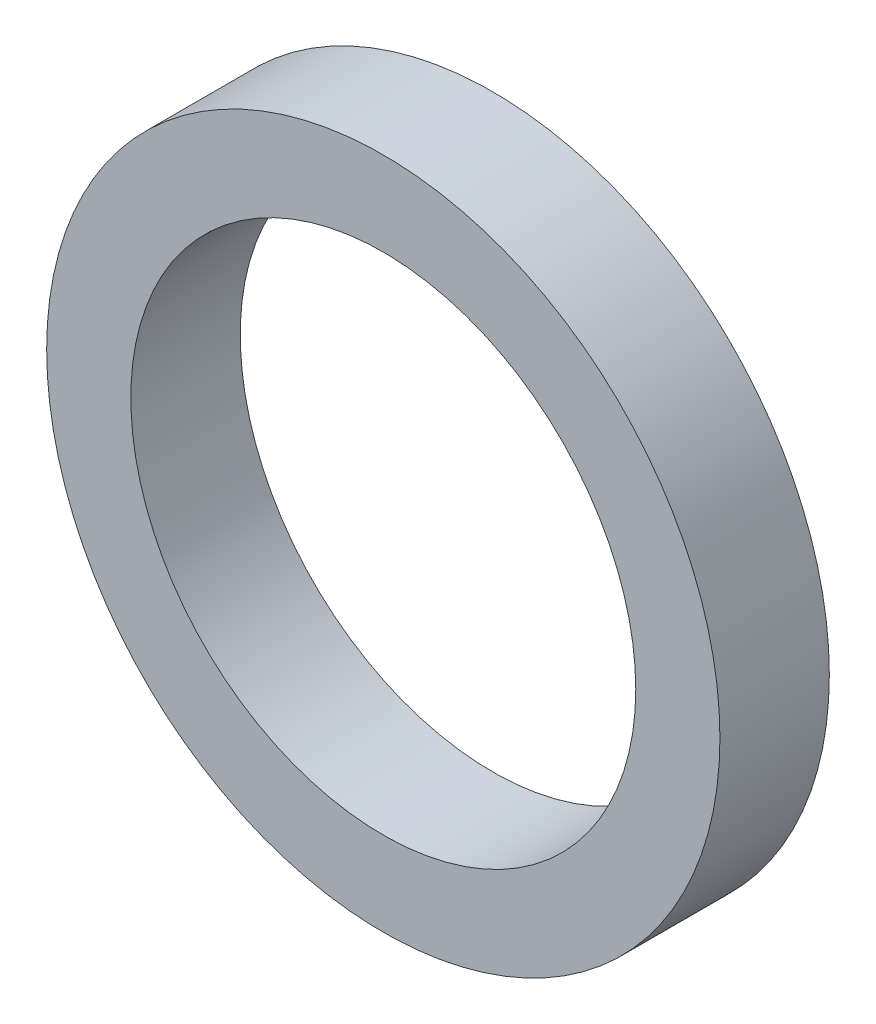
SolidWorks part; units mm, degrees
ref_plane "Płaszczyzna przednia" through (0, 0, 0) normal (0, 0, 1) x (1, 0, 0)
ref_plane "Płaszczyzna górna" through (0, 0, 0) normal (0, 1, 0) x (1, 0, 0)
ref_plane "Płaszczyzna prawa" through (0, 0, 0) normal (1, 0, 0) x (0, 0, -1)
sketch "Szkic1" plane through (0, 0, 0) normal (0, 0, 1) x (1, 0, 0)
  circle A0 centre (0, 0) radius 8
  circle A1 centre (0, 0) radius 6
extrude "Dodanie-wyciągnięcie1" add sketch "Szkic1" along normal blind 2.6
